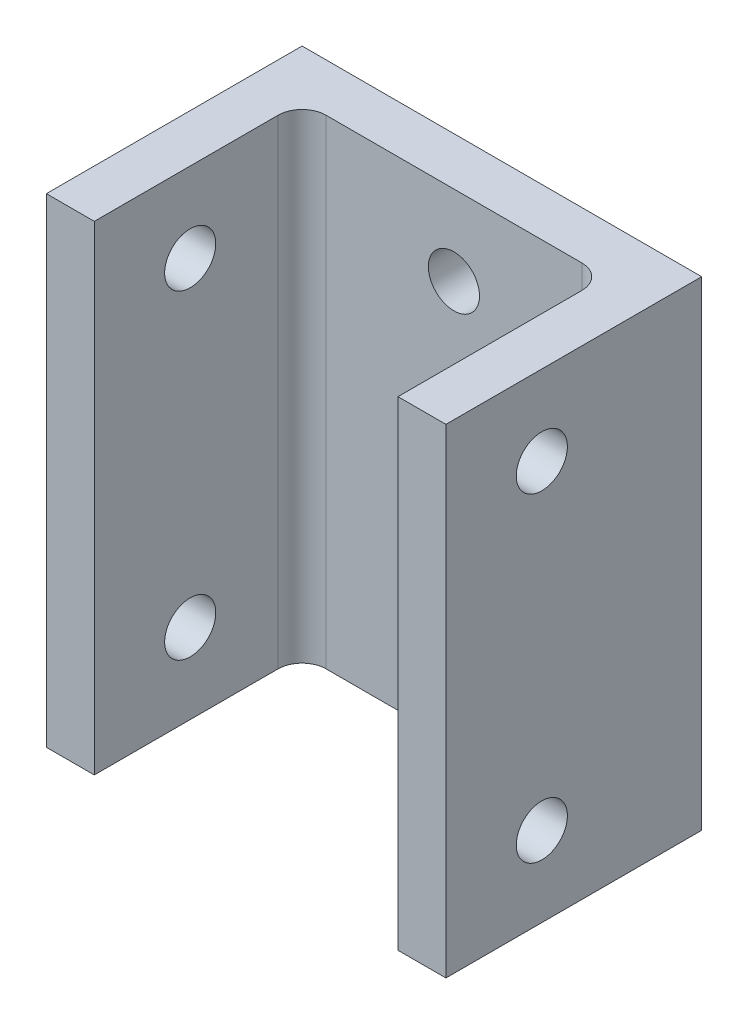
SolidWorks part; units mm, degrees
material "AISI 304"
ref_plane "前视基准面" through (0, 0, 0) normal (0, 0, 1) x (1, 0, 0)
ref_plane "上视基准面" through (0, 0, 0) normal (0, 1, 0) x (1, 0, 0)
ref_plane "右视基准面" through (0, 0, 0) normal (1, 0, 0) x (0, 0, -1)
sketch "草图1" plane through (0, 0, 0) normal (0, 0, 1) x (1, 0, 0)
  line L1 (253.9883, -73.1089) -> (278.9883, -73.1089)
  line L2 (253.9883, -73.1089) -> (253.9883, -43.1089)
  line L3 (253.9883, -43.1089) -> (278.9883, -43.1089)
  line L4 (278.9883, -73.1089) -> (278.9883, -43.1089)
  dimension "D1" = 25
  dimension "D2" = 30
extrude "凸台-拉伸1" add sketch "草图1" along normal blind 3
sketch "草图2" plane through (0, 0, 3) normal (0, 0, 1) x (1, 0, 0)
  line L0 (253.9883, -43.1089) -> (253.9883, -73.1089) construction
  line L1 (253.9883, -73.1089) -> (256.9883, -73.1089)
  line L2 (253.9883, -73.1089) -> (253.9883, -43.1089)
  line L3 (253.9883, -43.1089) -> (256.9883, -43.1089)
  line L4 (256.9883, -73.1089) -> (256.9883, -43.1089)
  line L5 (278.9883, -43.1089) -> (253.9883, -43.1089) construction
  line L6 (253.9883, -73.1089) -> (278.9883, -73.1089) construction
  line L7 (278.9883, -43.1089) -> (275.9883, -43.1089)
  line L8 (278.9883, -43.1089) -> (278.9883, -73.1089)
  line L9 (278.9883, -73.1089) -> (275.9883, -73.1089)
  line L10 (275.9883, -43.1089) -> (275.9883, -73.1089)
  dimension "D1" = 3
  dimension "D2" = 3
extrude "凸台-拉伸2" add sketch "草图2" along normal blind 15
sketch "草图3" plane through (253.9883, 0, 0) normal (-1, 0, 0) x (0, 0, 1)
  line L0 (18, -73.1089) -> (0, -73.1089) construction
  line L1 (18, -43.1089) -> (18, -73.1089) construction
  circle A0 centre (10, -48.1089) radius 1.6
  circle A1 centre (10, -68.1089) radius 1.6
  dimension "D1" = 3.2
  dimension "D2" = 3.2
  dimension "D3" = 20
  dimension "D4" = 5
  dimension "D5" = 8
  dimension "D6" = 8
extrude "切除-拉伸1" cut sketch "草图3" against normal blind 30
sketch "草图4" plane through (0, 0, 3) normal (0, 0, 1) x (1, 0, 0)
  line L1 (256.9883, -73.1089) -> (275.9883, -73.1089) construction
  line L2 (275.9883, -43.1089) -> (275.9883, -73.1089) construction
  circle A0 centre (266.4883, -48.1089) radius 1.6
  circle A1 centre (266.4883, -68.1089) radius 1.6
  dimension "D1" = 3.2
  dimension "D2" = 3.2
  dimension "D4" = 5
  dimension "D6" = 9.5
  dimension "D3" = 20
  dimension "D5" = 9.5
extrude "切除-拉伸2" cut sketch "草图4" against normal blind 30
sketch "草图5" plane through (253.9883, 0, 0) normal (-1, 0, 0) x (0, 0, 1)
  line L0 (18, -43.1089) -> (0, -43.1089) construction
  line L1 (16, -43.1089) -> (25.9736, -43.1089)
  line L2 (16, -43.1089) -> (16, -74.7139)
  line L3 (16, -74.7139) -> (25.9736, -74.7139)
  line L4 (25.9736, -43.1089) -> (25.9736, -74.7139)
  point P8 (0, 0)
extrude "切除-拉伸3" cut sketch "草图5" against normal blind 29
fillet "圆角1" radius 1.5 2 edges at (256.9883, -58.1089, 3) (275.9883, -58.1089, 3)
